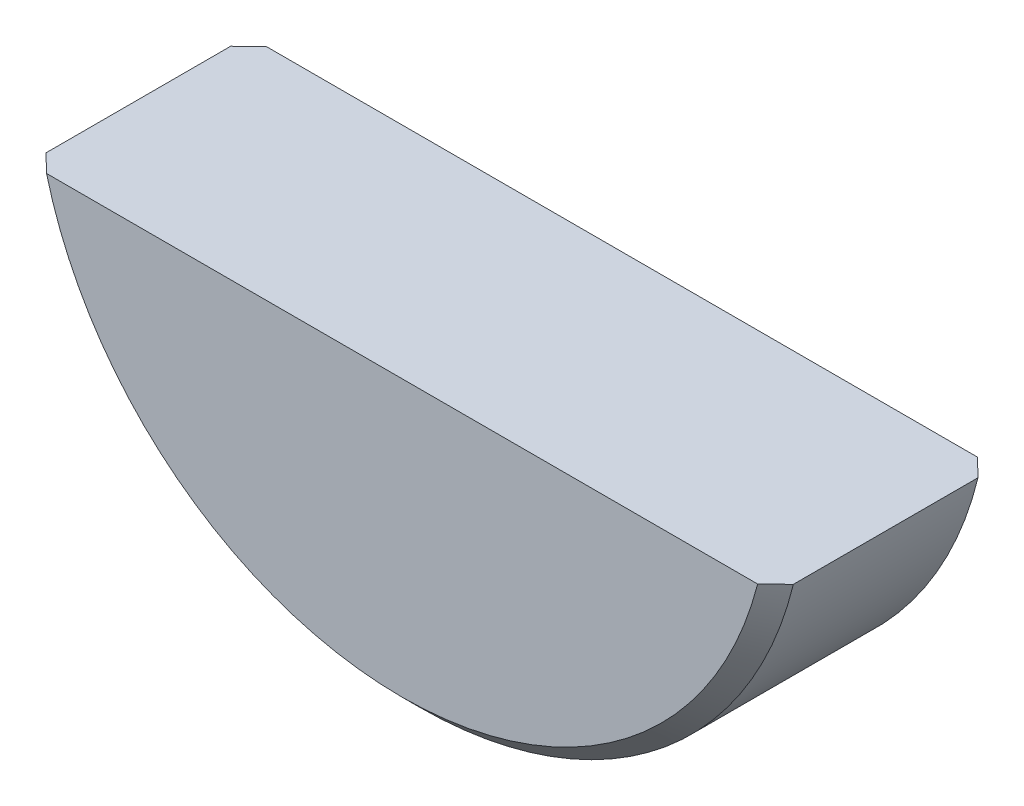
SolidWorks part; units mm, degrees
ref_plane "Front" through (0, 0, 0) normal (0, 0, 1) x (1, 0, 0)
ref_plane "Top" through (0, 0, 0) normal (0, 1, 0) x (1, 0, 0)
ref_plane "Right" through (0, 0, 0) normal (1, 0, 0) x (0, 0, -1)
sketch "Sketch1" plane through (0, 0, 0) normal (0, 0, 1) x (1, 0, 0)
  line L0 (-3.4, -0.8307) -> (3.4, -0.8307)
  arc A0 (-3.4, -0.8307) -> (3.4, -0.8307) centre (0, 0) ccw
  dimension "d1" = 7
  dimension "h" = 2.6693
extrude "BaseKey" add sketch "Sketch1" along normal mid plane 2
chamfer "Chamfer1" distance 0.16 angle 45 2 edges at (0, -3.5, 1) (0, -3.5, -1)
